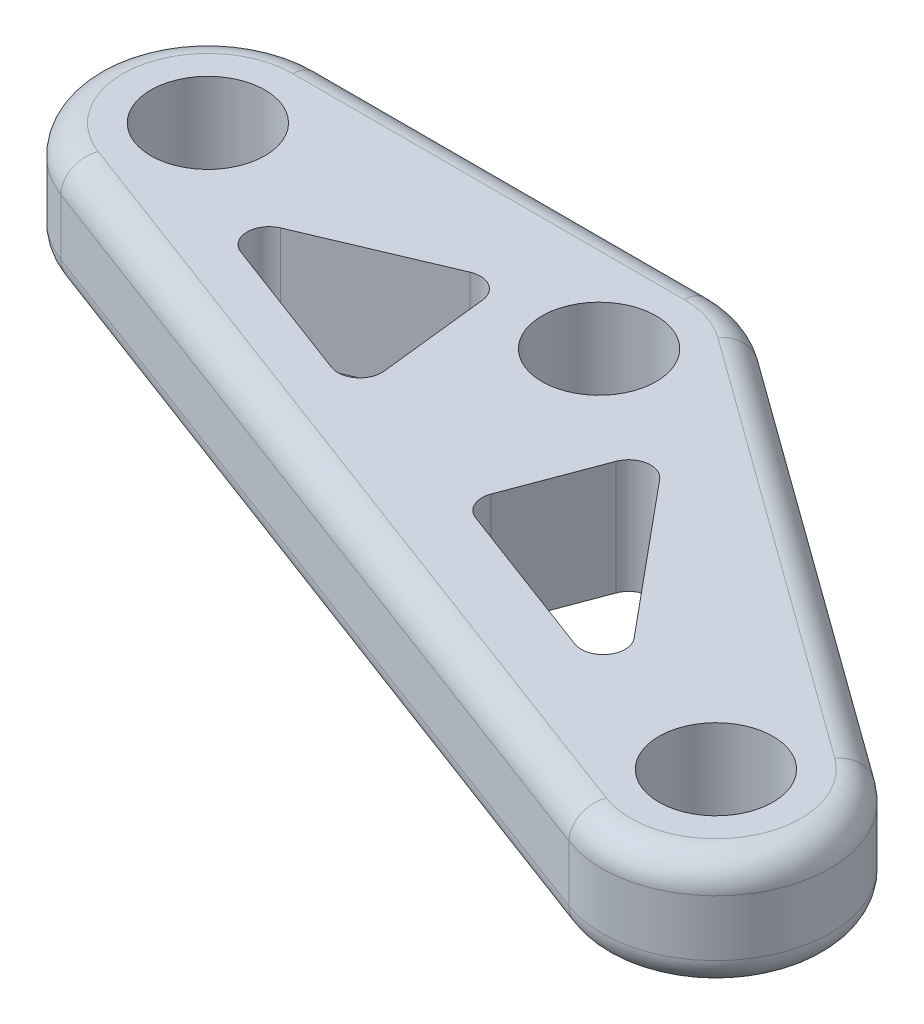
SolidWorks part; units mm, degrees
ref_plane "Front Plane" through (0, 0, 0) normal (0, 0, 1) x (1, 0, 0)
ref_plane "Top Plane" through (0, 0, 0) normal (0, 1, 0) x (1, 0, 0)
ref_plane "Right Plane" through (0, 0, 0) normal (1, 0, 0) x (0, 0, -1)
sketch "Sketch1" plane through (0, 0, 0) normal (0, 1, 0) x (1, 0, 0)
  line L0 (-37.807, -9.3611) -> (33.5246, -36.161)
  line L1 (42.9034, -18.698) -> (5.8617, 8.1019)
  line L2 (-34.29, 10) -> (0, 10)
  line L3 (37.0417, -26.7999) -> (0, 0) construction
  line L4 (0, 0) -> (-34.29, 0) construction
  line L5 (-34.29, 0) -> (37.0417, -26.7999) construction
  line L6 (-7.3733, -14.2442) -> (-27.5578, -6.6608)
  line L7 (-27.5578, -6.6608) -> (-9.0892, 1.1651)
  line L8 (-9.0892, 1.1651) -> (-7.3733, -14.2442)
  line L9 (10.448, -4.7064) -> (5.617, -17.5647)
  line L10 (5.617, -17.5647) -> (28.1474, -26.0296)
  line L11 (28.1474, -26.0296) -> (10.448, -4.7064)
  arc A0 (-37.807, -9.3611) -> (-34.29, 10) centre (-34.29, 0) cw
  arc A1 (5.8617, 8.1019) -> (0, 10) centre (0, 0) ccw
  arc A2 (33.5246, -36.161) -> (42.9034, -18.698) centre (37.0417, -26.7999) ccw
  circle A3 centre (-34.29, 0) radius 5
  circle A4 centre (0, 0) radius 5
  circle A5 centre (37.0417, -26.7999) radius 5
  point P15 (9.472, -3.5305)
  point P20 (0, 0)
  point P21 (27.1548, -24.8337)
  point P22 (2.5057, -17.2944)
  point P23 (0, 0)
  point P24 (-7.5232, 5.8932)
  point P25 (-27.8155, -5.8357)
  point P26 (-8.5102, 3.9759)
  point P27 (-27.8991, -7.4104)
  point P28 (-27.0668, -5)
  point P29 (-9.0892, 1.1651)
  point P30 (-27.5578, -6.6608)
  dimension "D4" = 10
  dimension "D5" = 10
  dimension "D1" = 76.2
  dimension "D2" = 34.29
  dimension "D3" = 45.72
extrude "Boss-Extrude1" add sketch "Sketch1" along normal blind 10
fillet "Fillet1" radius 2.54 12 edges at (-44.129, 0, -1.7873) (-17.145, 0, -10) (3.0807, 0, -9.5136) (24.3826, 0, 5.2981) (45.8515, 0, 31.5313) (-44.129, 10, -1.7873) (-17.145, 10, -10) (3.0807, 10, -9.5136) (24.3826, 10, 5.2981) (45.8515, 10, 31.5313) (-2.1412, 0, 22.761) (-2.1412, 10, 22.761)
scale "Scale1" scale about centroid uniform scaling yes scale factor 0.66
fillet "Fillet2" radius 1.27 6 edges at (4.4985, 5, 15.1172) (7.687, 5, 6.6307) (19.3686, 5, 20.704) (-4.0751, 5, 12.9257) (-17.3969, 5, 7.9206) (-5.2076, 5, 2.7556)
